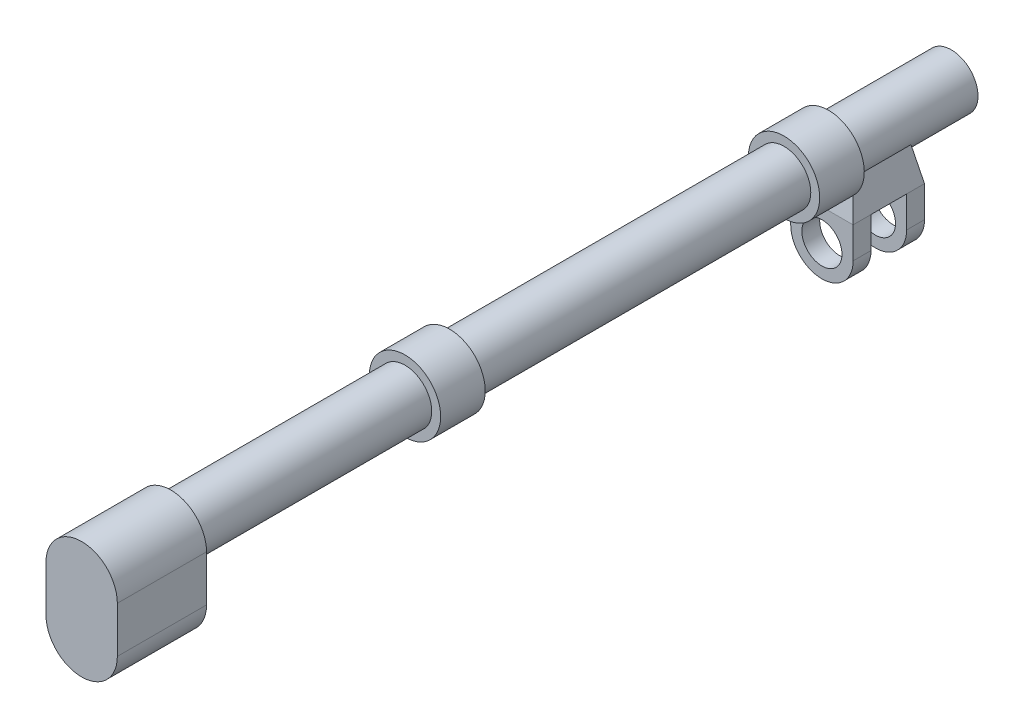
SolidWorks part; units mm, degrees
ref_plane "Front Plane" through (0, 0, 0) normal (0, 0, 1) x (1, 0, 0)
ref_plane "Top Plane" through (0, 0, 0) normal (0, 1, 0) x (1, 0, 0)
ref_plane "Right Plane" through (0, 0, 0) normal (1, 0, 0) x (0, 0, -1)
sketch "Sketch1" plane through (0, 0, 0) normal (0, 0, 1) x (1, 0, 0)
  circle A0 centre (0, 0) radius 6
  dimension "D1" = 12
extrude "Boss-Extrude1" add sketch "Sketch1" along normal mid plane 195
sketch "Sketch2" plane through (0, 0, 0) normal (0, 1, 0) x (1, 0, 0)
  line L1 (-5, 82.5) -> (5, 82.5)
  line L2 (-5, 82.5) -> (-5, 70.5)
  line L3 (-5, 70.5) -> (5, 70.5)
  line L4 (5, 82.5) -> (5, 70.5)
  line L7 (6, 97.5) -> (-6, 97.5) construction
  point P4 (0, 70.5)
  dimension "D1" = 10
  dimension "D2" = 12
  dimension "D3" = 15
ref_plane "Plane1" through (0, -10, 0) normal (0, 1, 0) x (-1, 0, 0)
sketch "Sketch3" plane through (0, -10, 0) normal (0, 1, 0) x (-1, 0, 0)
  line L0 (-6, -97.5) -> (6, -97.5) construction
  line L1 (-7, -68.5) -> (7, -68.5)
  line L2 (-7, -68.5) -> (-7, -84.5)
  line L3 (-7, -84.5) -> (7, -84.5)
  line L4 (7, -68.5) -> (7, -84.5)
  line L5 (5, -70.5) -> (-5, -70.5) construction
  point P4 (0, -68.5)
  dimension "D1" = 13
  dimension "D2" = 2
  dimension "D3" = 14
  dimension "D4" = 16
loft "Loft1" add profiles "Sketch2", "Sketch3" connector at (5, 0, -70.5) connector at (7, -10, -68.5)
sketch "Sketch4" plane through (0, -10, 0) normal (0, -1, 0) x (1, 0, 0)
  line L0 (-18.0587, -76.5) -> (19.7034, -76.5) construction
  line L1 (7, -68.5) -> (7, -84.5) construction
  line L2 (-7, -72.5) -> (7, -72.5)
  line L3 (-7, -84.5) -> (-7, -68.5) construction
  line L4 (-7, -72.5) -> (-7, -68.5)
  line L5 (-7, -68.5) -> (7, -68.5)
  line L6 (7, -68.5) -> (7, -72.5)
  line L7 (7, -84.5) -> (7, -80.5)
  line L8 (-7, -84.5) -> (7, -84.5)
  line L9 (-7, -80.5) -> (-7, -84.5)
  line L10 (-7, -80.5) -> (7, -80.5)
  point P4 (7, -76.5)
  dimension "D1" = 4
extrude "Boss-Extrude2" add sketch "Sketch4" along normal blind 14 contours L2 | L10 region at (0, -10, -70.5) region at (0, -10, -82.5)
sketch "Sketch5" plane through (0, 0, -72.5) normal (0, 0, -1) x (-1, 0, 0)
  line L1 (7, -24) -> (-7, -24) construction
  line L2 (-7, -24) -> (-7, -10) construction
  circle A0 centre (0, -17) radius 4.5
  point P6 (0, -24)
  point P7 (-7, -17)
  dimension "D1" = 9
extrude "Cut-Extrude1" cut sketch "Sketch5" against normal blind 4
sketch "Sketch6" plane through (0, 0, -80.5) normal (0, 0, 1) x (1, 0, 0)
  line L0 (7, -24) -> (7, -10) construction
  line L1 (-7, -24) -> (7, -24) construction
  circle A0 centre (0, -17) radius 4.5
  point P2 (7, -17)
  point P7 (0, -24)
  dimension "D1" = 9
extrude "Cut-Extrude2" cut sketch "Sketch6" against normal blind 4
sketch "Sketch7" plane through (0, 0, -68.5) normal (0, 0, 1) x (1, 0, 0)
  line L0 (7, -24) -> (-7, -24) construction
  line L1 (-7, -24) -> (-7, -10) construction
  line L2 (-7, -17) -> (-7, -24)
  line L3 (-7, -24) -> (7, -24)
  line L4 (7, -24) -> (7, -17)
  arc A0 (-7, -17) -> (7, -17) centre (0, -17) ccw
  line M3 (-7, -10) -> (-7, -24)
  line M5 (7, -24) -> (7, -10)
extrude "Cut-Extrude3" cut sketch "Sketch7" against normal through all contours A0 M3 | A0 L3 M5 region at (-5.4364, -22.4364, -68.5) region at (5.4364, -22.4364, -68.5)
ref_plane "Plane2" through (0, 0, -65) normal (0, 0, 1) x (1, 0, 0)
sketch "Sketch8" plane through (0, 0, -65) normal (0, 0, 1) x (1, 0, 0)
  circle A0 centre (0, 0) radius 8
  dimension "D1" = 16
extrude "Boss-Extrude3" add sketch "Sketch8" along normal mid plane 10
sketch "Sketch9" plane through (0, 0, 97.5) normal (0, 0, 1) x (1, 0, 0)
  line L0 (-8, 0) -> (-8, -10.3158)
  line L2 (8, -10.3158) -> (8, 0)
  circle A0 centre (0, 0) radius 8
  arc A1 (-8, -10.3158) -> (8, -10.3158) centre (0, -10.3158) ccw
  circle A2 centre (0, 0) radius 8 construction
  circle M1 centre (0, 0) radius 6
extrude "Boss-Extrude4" add sketch "Sketch9" against normal blind 20 contours A0 M1 | L0 A1 L2 A0 region at (0, -11.4411, 97.5) region at (0, 7.7737, 97.5)
ref_plane "Plane3" through (0, 0, 15) normal (0, 0, 1) x (1, 0, 0)
sketch "Sketch11" plane through (0, 0, 15) normal (0, 0, 1) x (1, 0, 0)
  circle A0 centre (0, 0) radius 8
extrude "Boss-Extrude5" add sketch "Sketch11" along normal blind 10
